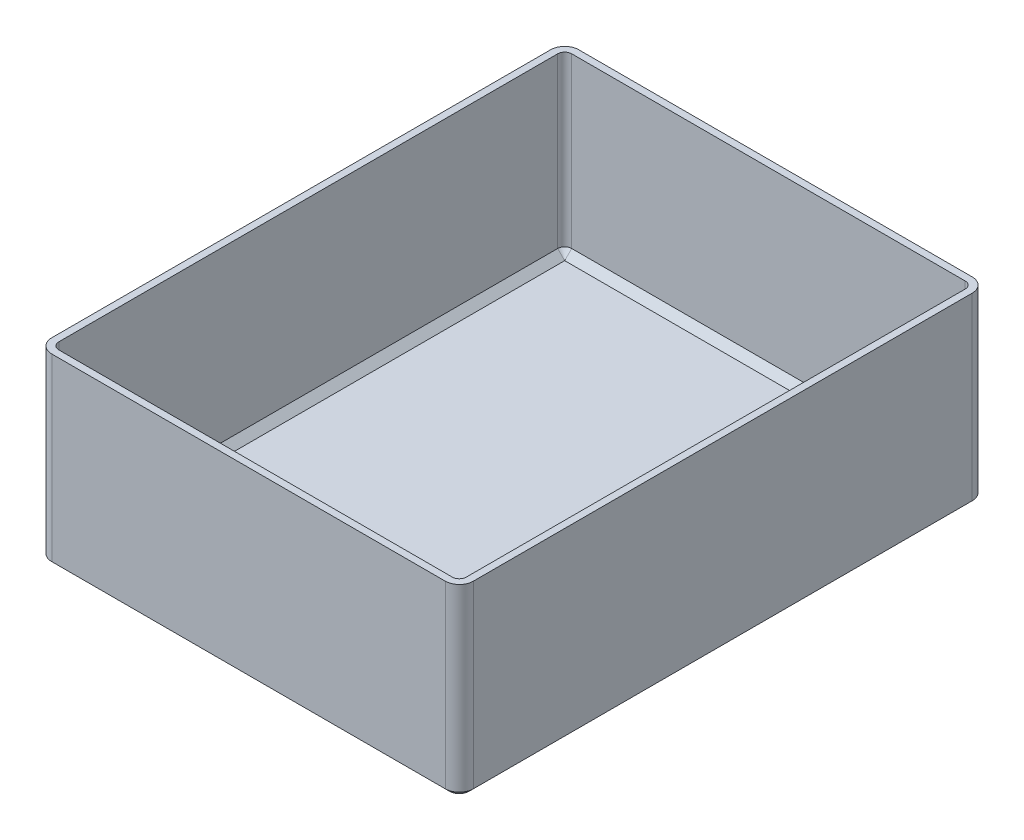
SolidWorks part; units mm, degrees
ref_plane "前视基准面" through (0, 0, 0) normal (0, 0, 1) x (1, 0, 0)
ref_plane "上视基准面" through (0, 0, 0) normal (0, 1, 0) x (1, 0, 0)
ref_plane "右视基准面" through (0, 0, 0) normal (1, 0, 0) x (0, 0, -1)
other "Configuration Table"
sketch "草图1" plane through (0, 0, 0) normal (0, 1, 0) x (1, 0, 0)
  line L1 (4, 0) -> (116, 0)
  line L2 (0, -4) -> (0, -146)
  line L3 (4, -150) -> (116, -150)
  line L4 (120, -4) -> (120, -146)
  arc A0 (116, -150) -> (120, -146) centre (116, -146) ccw
  arc A1 (0, -146) -> (4, -150) centre (4, -146) ccw
  arc A2 (116, 0) -> (120, -4) centre (116, -4) cw
  arc A3 (4, 0) -> (0, -4) centre (4, -4) ccw
  point P7 (120, -150)
  point P12 (120, 0)
  point P15 (0, 0)
  dimension "D3" = 4
  dimension "D1" = 120
  dimension "D2" = 150
extrude "凸台-拉伸1" add sketch "草图1" along normal blind 2.4
sketch "草图2" plane through (0, 2.4, 0) normal (0, 1, 0) x (1, 0, 0)
  line L12 (2, -4) -> (2, -146)
  line L13 (4, -148) -> (116, -148)
  line L14 (118, -146) -> (118, -4)
  line L15 (116, -2) -> (4, -2)
  line L16 (120, -146) -> (120, -4)
  line L17 (116, 0) -> (4, 0)
  line L18 (0, -4) -> (0, -146)
  line L19 (4, -150) -> (116, -150)
  line L20 (120, -146) -> (120, -4)
  line L21 (116, 0) -> (4, 0)
  line L22 (0, -4) -> (0, -146)
  line L23 (4, -150) -> (116, -150)
  arc A4 (2, -146) -> (4, -148) centre (4, -146) ccw
  arc A5 (116, -148) -> (118, -146) centre (116, -146) ccw
  arc A6 (118, -4) -> (116, -2) centre (116, -4) ccw
  arc A7 (4, -2) -> (2, -4) centre (4, -4) ccw
  arc A8 (116, -150) -> (120, -146) centre (116, -146) ccw
  arc A9 (120, -4) -> (116, 0) centre (116, -4) ccw
  arc A10 (4, 0) -> (0, -4) centre (4, -4) ccw
  arc A11 (0, -146) -> (4, -150) centre (4, -146) ccw
  arc A12 (116, -150) -> (120, -146) centre (116, -146) ccw
  arc A13 (120, -4) -> (116, 0) centre (116, -4) ccw
  arc A14 (4, 0) -> (0, -4) centre (4, -4) ccw
  arc A15 (0, -146) -> (4, -150) centre (4, -146) ccw
  dimension "D1" = 0
  dimension "D2" = 2
extrude "凸台-拉伸2" add sketch "草图2" along normal blind 50
chamfer "倒角2" distance 1.2 angle 45 8 edges at (60, 0, 150) (120, 0, 75) (60, 0, 0) (0, 0, 75) (118.8284, 0, 1.1716) (1.1716, 0, 1.1716) (1.1716, 0, 148.8284) (118.8284, 0, 148.8284)
chamfer "倒角5" distance 2 angle 45 8 edges at (60, 2.4, 148) (117.4142, 2.4, 147.4142) (2.5858, 2.4, 147.4142) (118, 2.4, 75) (2, 2.4, 75) (117.4142, 2.4, 2.5858) (2.5858, 2.4, 2.5858) (60, 2.4, 2)
ref_plane "基准面1" through (0, 10, 0) normal (0, -1, 0) x (-1, 0, 0)
sketch "草图4" plane through (0, 10, 0) normal (0, -1, 0) x (-1, 0, 0)
  line L0 (-116, 0) -> (-4, 0) construction
  line L1 (-90, 0) -> (-30, 0)
  line L2 (-90, 0) -> (-90, 4)
  line L3 (-90, 4) -> (-30, 4)
  line L4 (-30, 0) -> (-30, 4)
  line L5 (-120, -146) -> (-120, -4) construction
  dimension "D1" = 60
  dimension "D2" = 4
  dimension "D3" = 30
extrude "凸台-拉伸3" add sketch "草图4" against normal blind 3
chamfer "倒角3" distance 4 angle 45 1 edges at (60, 10, 0)
sketch "草图5" plane through (0, 13, 0) normal (0, 1, 0) x (1, 0, 0)
  line L0 (90, 0) -> (30, 0) construction
  line L1 (30, 4) -> (32, 4)
  line L2 (30, 4) -> (30, 0)
  line L3 (30, 0) -> (32, 0)
  line L4 (32, 2) -> (32, 0)
  line L6 (90, 4) -> (88, 4)
  line L7 (90, 4) -> (90, 0)
  line L8 (90, 0) -> (88, 0)
  line L9 (88, 2) -> (88, 0)
  line L11 (32, 4) -> (36, 4)
  line L13 (32, 2) -> (36, 2)
  line L14 (36, 4) -> (36, 2)
  line L15 (88, 4) -> (84, 4)
  line L17 (88, 2) -> (84, 2)
  line L18 (84, 4) -> (84, 2)
  dimension "D1" = 2
  dimension "D2" = 2
  dimension "D3" = 2
  dimension "D4" = 4
  dimension "D5" = 2
  dimension "4" = 4
extrude "凸台-拉伸4" add sketch "草图5" along normal blind 30
chamfer "倒角4" distance 4 angle 45 2 edges at (30, 24.5, 0) (90, 24.5, 0)
sketch "草图6" plane through (0, 13, 0) normal (0, 1, 0) x (1, 0, 0)
  line L1 (36, 4) -> (84, 4)
  line L2 (36, 4) -> (36, 2)
  line L3 (36, 2) -> (84, 2)
  line L4 (84, 4) -> (84, 2)
extrude "凸台-拉伸5" add sketch "草图6" along normal blind 3
equation "\"D1@草图4\"=120-60"
